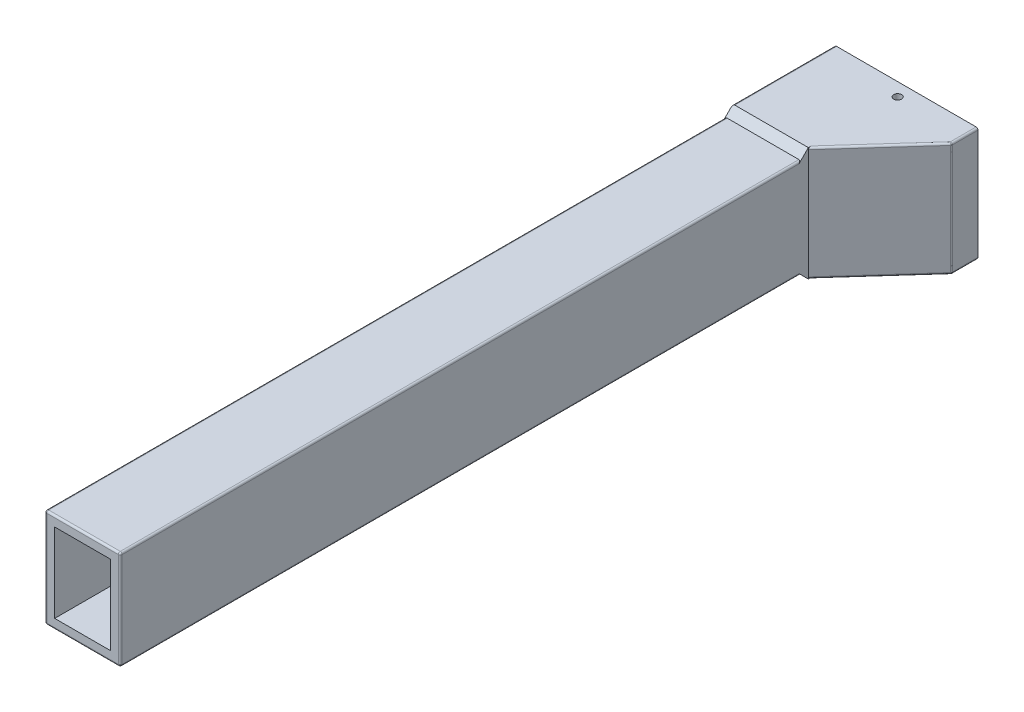
SolidWorks part; units mm, degrees
note: '?' marks a value the reader was unsure of.
material "PET"
ref_plane "Front Plane" through (0, 0, 0) normal (0, 0, 1) x (1, 0, 0)
ref_plane "Top Plane" through (0, 0, 0) normal (0, 1, 0) x (1, 0, 0)
ref_plane "Right Plane" through (0, 0, 0) normal (1, 0, 0) x (0, 0, -1)
sketch "Sketch1" plane through (0, 0, 0) normal (0, 0, 1) x (1, 0, 0)
  line L0 (9.1, 11.3) -> (9.1, -11.3) construction
  line L1 (9.1, 11.3) -> (9.1, -11.3) construction
  line L2 (8.1, -10.3) -> (-6.3, -10.3) construction
  line L3 (8.1, -10.3) -> (-6.3, -10.3) construction
  line L13 (28.9, -13.1) -> (28.9, 13.1) construction
  line L15 (-9.1, -13.1) -> (28.9, -13.1) construction
  line L24 (-6.3, -10.3) -> (-6.3, 10.3) construction
  line L27 (-6.3, -10.3) -> (-6.3, 10.3) construction
  line L29 (-6.3, 10.3) -> (8.1, 10.3) construction
  line L30 (28, -12.2) -> (28, 12.2) construction
  line L31 (-7.3, -11.3) -> (-7.3, 11.3) construction
  line L32 (-7.3, -11.3) -> (-7.3, 11.3) construction
  line L33 (27.1, 11.3) -> (27.1, -11.3) construction
  line L34 (-8.2, -12.2) -> (28, -12.2) construction
  line L36 (28, 12.2) -> (-8.2, 12.2) construction
  line L37 (-7.3, 11.3) -> (9.1, 11.3) construction
  line L38 (-8.2, 12.2) -> (-8.2, -12.2) construction
  line L39 (28, -12.2) -> (28, 12.2) construction
  line L40 (27.1, 11.3) -> (27.1, -11.3) construction
  line L41 (-8.2, -12.2) -> (28, -12.2) construction
  line L42 (27.1, -11.3) -> (-7.3, -11.3) construction
  line L43 (28, 12.2) -> (-8.2, 12.2) construction
  line L44 (-7.3, 11.3) -> (27.1, 11.3) construction
  line L45 (-7.3, -11.3) -> (-7.3, 11.3) construction
  line L46 (-8.2, 12.2) -> (-8.2, -12.2) construction
  line L47 (-6.3, 10.3) -> (8.1, 10.3) construction
  line L48 (8.1, 10.3) -> (8.1, -10.3) construction
  line L49 (8.1, 10.3) -> (8.1, -10.3) construction
  line L50 (-6.5, 10.5) -> (8.3, 10.5)
  line L51 (8.3, 10.5) -> (8.3, -10.5)
  line L52 (8.3, -10.5) -> (-6.5, -10.5)
  line L53 (-6.5, -10.5) -> (-6.5, 10.5)
  line L54 (8.1, 10.3) -> (8.3, 10.3) construction
  line L55 (8.1, 10.3) -> (8.1, 10.5) construction
  line L56 (-6.3, -10.3) -> (-6.3, -10.5) construction
  line L57 (-6.3, -10.3) -> (-6.5, -10.3) construction
  line L58 (-6.5, 10.5) -> (-9.1, 10.5) construction
  line L59 (10.9, 13.1) -> (10.9, -13.1)
  line L60 (8.3, 10.5) -> (10.9, 10.5) construction
  line L61 (-9.1, 13.1) -> (10.9, 13.1)
  line L62 (-9.1, -13.1) -> (10.9, -13.1)
  line L67 (28.9, -13.1) -> (28.9, 13.1)
  line L68 (-9.1, -13.1) -> (28.9, -13.1)
  line L69 (-9.1, 13.1) -> (-9.1, -13.1)
  line L70 (28.9, 13.1) -> (-9.1, 13.1)
  line L71 (28.9, -13.1) -> (28.9, 13.1) construction
  line L73 (-9.1, 13.1) -> (-9.1, -13.1)
  line L74 (28.9, 13.1) -> (-9.1, 13.1) construction
  dimension "D1" = 0.2
  dimension "D2" = 0
extrude "Top" add sketch "Sketch1" against normal blind 20
sketch "Sketch2" plane through (0, 0, -20) normal (0, 0, -1) x (-1, 0, 0)
  line L0 (9.1, 13.1) -> (9.1, -13.1) construction
  line L2 (9.1, -13.1) -> (-10.9, -13.1) construction
  line L4 (-10.9, 13.1) -> (9.1, 13.1) construction
  line L5 (-10.9, -13.1) -> (-10.9, 13.1) construction
  line L7 (9.1, 13.1) -> (9.1, -13.1)
  line L12 (9.1, -13.1) -> (-10.9, -13.1)
  line L14 (-10.9, 13.1) -> (9.1, 13.1)
  line L21 (-10.9, -13.1) -> (-10.9, 13.1)
  line L23 (7.3, -11.3) -> (7.3, 11.3) construction
  line L24 (7.3, -11.3) -> (7.3, 11.3)
  line L25 (-27.1, -11.3) -> (7.3, -11.3) construction
  line L26 (-9.1, -11.3) -> (7.3, -11.3)
  line L27 (7.3, 11.3) -> (-27.1, 11.3) construction
  line L28 (7.3, 11.3) -> (-9.1, 11.3)
  line L31 (-9.1, -11.3) -> (-9.1, 11.3)
  line L42 (-9.1, -11.3) -> (-10.9, -11.3) construction
  line L43 (7.3, -11.3) -> (9.1, -11.3) construction
extrude "Body" add sketch "Sketch2" along normal blind 162.5
sketch "Sketch8" plane through (0, 0, -182.5) normal (0, 0, -1) x (-1, 0, 0)
  line L4 (9.1, 13.1) -> (-10.9, 13.1)
  line L5 (-10.9, 13.1) -> (-10.9, -13.1)
  line L6 (-10.9, -13.1) -> (9.1, -13.1)
  line L7 (9.1, -13.1) -> (9.1, 13.1)
  line L8 (9.1, 13.1) -> (-10.9, 13.1)
  line L9 (-10.9, 13.1) -> (-10.9, -13.1)
  line L10 (-10.9, -13.1) -> (9.1, -13.1)
  line L11 (9.1, -13.1) -> (9.1, 13.1)
  dimension "D1" = 0
ref_plane "Plane1" through (0, 0, -202.5) normal (0, 0, -1) x (-1, 0, 0)
sketch "Sketch11" plane through (0, 0, -182.5) normal (0, 0, -1) x (-1, 0, 0)
  line L4 (-9.1, 11.3) -> (-9.1, -11.3) construction
  line L5 (7.3, 11.3) -> (-9.1, 11.3) construction
  line L6 (-9.1, -11.3) -> (7.3, -11.3) construction
  line L7 (7.3, -11.3) -> (7.3, 11.3) construction
  line L16 (-9.1, 11.3) -> (-9.1, -11.3)
  line L17 (7.3, 11.3) -> (-9.1, 11.3)
  line L18 (-9.1, -11.3) -> (7.3, -11.3)
  line L19 (7.3, -11.3) -> (7.3, 11.3)
sketch "Sketch12" plane through (0, 0, -202.5) normal (0, 0, -1) x (-1, 0, 0)
  line L9 (7.3, -11.3) -> (7.3, 11.3) construction
  line L10 (7.3, -11.3) -> (7.3, 11.3)
  line L11 (-27.1, -11.3) -> (7.3, -11.3) construction
  line L12 (-27.1, -11.3) -> (7.3, -11.3)
  line L13 (7.3, 11.3) -> (-27.1, 11.3) construction
  line L14 (7.3, 11.3) -> (-27.1, 11.3)
  line L15 (-27.1, 11.3) -> (-27.1, -11.3) construction
  line L16 (-27.1, 11.3) -> (-27.1, -11.3)
sketch "Sketch10" plane through (0, 0, -202.5) normal (0, 0, -1) x (-1, 0, 0)
  line L0 (9.1, 13.1) -> (9.1, -13.1) construction
  line L4 (-10.9, 13.1) -> (-10.9, -13.1)
  line L5 (-10.9, -13.1) -> (9.1, -13.1)
  line L6 (9.1, -13.1) -> (9.1, 13.1)
  line L7 (9.1, 13.1) -> (-10.9, 13.1)
  line L9 (-28.9, -13.1) -> (9.1, -13.1)
  line L11 (9.1, 13.1) -> (-28.9, 13.1)
  line L20 (-28.9, -13.1) -> (-28.9, 13.1) construction
  line L21 (9.1, 13.1) -> (9.1, -13.1)
  line L24 (-28.9, -13.1) -> (-28.9, 13.1)
  dimension "D1" = 0
loft "Loft3" add profiles "Sketch10", "Sketch8"
loft "Cut-Loft1" cut profiles "Sketch12", "Sketch11"
sketch "Sketch13" plane through (0, 0, -202.5) normal (0, 0, -1) x (-1, 0, 0)
  line L0 (-28.9, -13.1) -> (-28.9, 13.1) construction
  line L1 (-28.9, -13.1) -> (-28.9, 13.1)
  line L2 (-28.9, 13.1) -> (9.1, 13.1) construction
  line L3 (-28.9, 13.1) -> (9.1, 13.1)
  line L5 (9.1, -13.1) -> (-28.9, -13.1)
  line L6 (9.1, 13.1) -> (9.1, -13.1) construction
  line L7 (9.1, 13.1) -> (9.1, -13.1)
  line L8 (8.2, 12.2) -> (8.2, -12.2) construction
  line L9 (8.2, 12.2) -> (8.2, -12.2) construction
  line L10 (8.2, -12.2) -> (-28, -12.2) construction
  line L11 (8.2, -12.2) -> (-28, -12.2) construction
  line L12 (-28, 12.2) -> (8.2, 12.2) construction
  line L13 (-28, 12.2) -> (8.2, 12.2) construction
  line L15 (-28, -12.2) -> (-28, 12.2) construction
  line L16 (-28, -12.2) -> (-28, 12.2) construction
  line L17 (-28.05, 12.25) -> (8.25, 12.25)
  line L18 (8.25, 12.25) -> (8.25, -12.25)
  line L19 (8.25, -12.25) -> (-28.05, -12.25)
  line L20 (-28.05, -12.25) -> (-28.05, 12.25)
  line L21 (-28, -12.2) -> (-28, -12.25) construction
  line L22 (-28, -12.2) -> (-28.05, -12.2) construction
  line L23 (8.2, 12.2) -> (8.25, 12.2) construction
  line L24 (8.2, 12.2) -> (8.2, 12.25) construction
  dimension "D1" = 0.05
extrude "Insert" add sketch "Sketch13" along normal blind 7
sketch "Sketch14" plane through (0, 0, 0) normal (0, 0, 1) x (1, 0, 0)
  line L0 (-9.1, -13.1) -> (10.9, 13.1) construction
  point P4 (0.9, 0)
ref_axis "Axis1" through (0.9, 0, 0) along (0, 0, 1)?
sketch "Sketch15" plane through (0, 0, 0) normal (0, 1, 0) x (1, 0, 0)
  circle A0 centre (11.1, 206) radius 1.05
  circle A5 centre (11.1, 206) radius 0.9
  circle A6 centre (11.1, 206) radius 0.9 construction
  dimension "D1" = 2.1
  dimension "D2" = 0
extrude "Cut-Extrude1" cut sketch "Sketch15" against normal through all both and the other way through all
sketch "Sketch16" plane through (0, 0, 0) normal (0, 1, 0) x (1, 0, 0)
  line L0 (27.1, 202.5) -> (9.1, 182.5) construction
  line L1 (9.1, 202.5) -> (9.1, 182.5) construction
  line L2 (13.1, 186.9444) -> (9.1, 182.5) construction
  line L3 (13.1, 202.5) -> (13.1, 186.9444) construction
  line L4 (13.1, 202.5) -> (9.1, 202.5) construction
  line L5 (13.1, 202.5) -> (9.1, 202.5) construction
sketch "Sketch17" plane through (0, 11.3, 0) normal (0, -1, 0) x (1, 0, 0)
  line L0 (13.1, -202.5) -> (13.1, -186.9444) construction
  line L1 (13.1, -202.5) -> (13.1, -186.9444)
  line L2 (9.1, -202.5) -> (9.1, -182.5) construction
  line L3 (9.1, -202.5) -> (9.1, -182.5)
  line L4 (13.1, -202.5) -> (9.1, -202.5) construction
  line L5 (13.1, -202.5) -> (9.1, -202.5)
  line L6 (13.1, -186.9444) -> (9.1, -182.5) construction
  line L7 (13.1, -186.9444) -> (9.1, -182.5)
extrude "Boss-Extrude1" add sketch "Sketch17" along normal blind 2
sketch "Sketch18" plane through (0, -11.3, 0) normal (0, 1, 0) x (1, 0, 0)
  line L0 (13.1, 202.5) -> (9.1, 202.5) construction
  line L1 (13.1, 202.5) -> (9.1, 202.5)
  line L2 (9.1, 202.5) -> (9.1, 182.5) construction
  line L3 (9.1, 202.5) -> (9.1, 182.5)
  line L4 (13.1, 202.5) -> (13.1, 186.9444) construction
  line L5 (13.1, 202.5) -> (13.1, 186.9444)
  line L6 (13.1, 186.9444) -> (9.1, 182.5) construction
  line L7 (13.1, 186.9444) -> (9.1, 182.5)
extrude "Boss-Extrude2" add sketch "Sketch18" along normal blind 2
sketch "Sketch19" plane through (0, -13.1, 0) normal (0, -1, 0) x (1, 0, 0)
  line L0 (28.9, -209.5) -> (-9.1, -209.5) construction
  line L1 (28.9, -209.5) -> (-9.1, -209.5)
  line L2 (28.9, -209.5) -> (28.9, -202.5) construction
  line L3 (28.9, -209.5) -> (28.9, -202.5)
  line L4 (28.9, -202.5) -> (10.9, -182.5) construction
  line L5 (28.9, -202.5) -> (10.9, -182.5)
  line L6 (-9.1, -209.5) -> (-9.1, 0) construction
  line L7 (-9.1, -209.5) -> (-9.1, -182.5)
  line L8 (10.9, -182.5) -> (-9.1, -182.5)
  circle A0 centre (11.1, -206) radius 1.05 construction
  circle A1 centre (11.1, -206) radius 1.05
extrude "Boss-Extrude3" add sketch "Sketch19" along normal blind 2
sketch "Sketch20" plane through (0, 13.1, 0) normal (0, 1, 0) x (1, 0, 0)
  line L0 (-9.1, 209.5) -> (28.9, 209.5) construction
  line L1 (-9.1, 209.5) -> (28.9, 209.5)
  line L2 (28.9, 209.5) -> (28.9, 202.5) construction
  line L3 (28.9, 209.5) -> (28.9, 202.5)
  line L4 (28.9, 202.5) -> (10.9, 182.5) construction
  line L5 (28.9, 202.5) -> (10.9, 182.5)
  line L6 (-9.1, 209.5) -> (-9.1, 0) construction
  line L7 (-9.1, 209.5) -> (-9.1, 182.5)
  line L8 (10.9, 182.5) -> (-9.1, 182.5)
  circle A0 centre (11.1, 206) radius 1.05 construction
  circle A1 centre (11.1, 206) radius 1.05
extrude "Boss-Extrude4" add sketch "Sketch20" along normal blind 2
chamfer "Chamfer1" distance 2 angle 45 2 edges at (0.9, 13.1, -182.5) (0.9, -13.1, -182.5)
fillet "Fillet1" radius 0.5 17 edges at (10.9, -13.1, -90.25) (10.9, 13.1, -90.25) (10.9, 0, 0) (0.9, -13.1, 0) (0.9, 13.1, 0) (-9.1, 0, 0) (19.9, 15.1, -192.5) (19.9, -15.1, -192.5) (28.9, 15.1, -206) (28.9, -15.1, -206) (-9.1, -15.1, -196) (-9.1, 15.1, -196)
